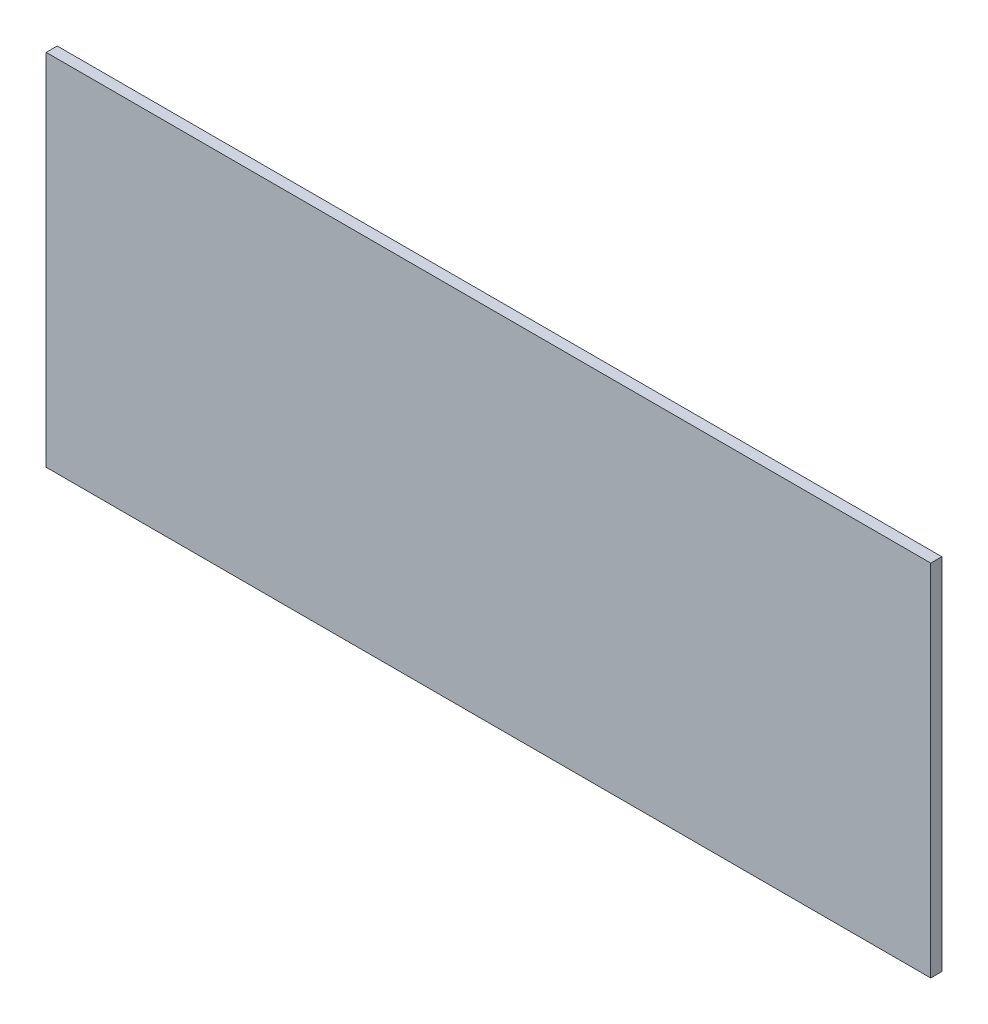
SolidWorks part; units mm, degrees
ref_plane "Alzado" through (0, 0, 0) normal (0, 0, 1) x (1, 0, 0)
ref_plane "Planta" through (0, 0, 0) normal (0, 1, 0) x (1, 0, 0)
ref_plane "Vista lateral" through (0, 0, 0) normal (1, 0, 0) x (0, 0, -1)
sketch "Croquis1" plane through (0, 0, 0) normal (0, 0, 1) x (1, 0, 0)
  line L1 (-80, 32.5) -> (80, 32.5)
  line L2 (-80, 32.5) -> (-80, -32.5)
  line L3 (-80, -32.5) -> (80, -32.5)
  line L4 (80, 32.5) -> (80, -32.5)
  line L5 (-80, 32.5) -> (80, -32.5) construction
  line L6 (-80, -32.5) -> (80, 32.5) construction
  point P0 (0, 0)
  dimension "D1" = 65
  dimension "D2" = 160
extrude "Saliente-Extruir1" add sketch "Croquis1" along normal blind 2
equation "\"D1@Croquis1\"=65"
equation "\"D1@Saliente-Extruir1\"= \"GROSOR_PARED_IMPRESION\""
equation "\"GROSOR_PARED_IMPRESION\"=2"
equation "\"TOLERANCIA\"= 0.05"
